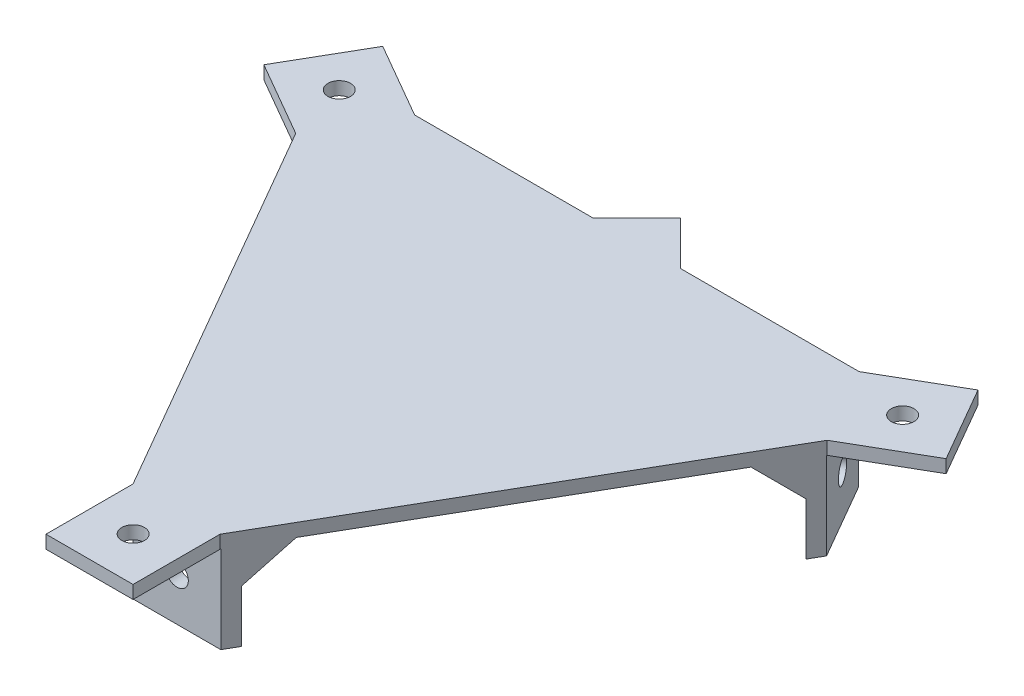
SolidWorks part; units mm, degrees
ref_plane "Ebene vorne" through (0, 0, 0) normal (0, 0, 1) x (1, 0, 0)
ref_plane "Ebene oben" through (0, 0, 0) normal (0, 1, 0) x (1, 0, 0)
ref_plane "Ebene rechts" through (0, 0, 0) normal (1, 0, 0) x (0, 0, -1)
sketch "Skizze1" plane through (0, 0, 0) normal (0, 1, 0) x (1, 0, 0)
  line L0 (0, 0) -> (73.385, 42.3688) construction
  line L1 (73.385, 42.3688) -> (0, -84.7377) construction
  line L2 (0, -84.7377) -> (0, 0) construction
  line L3 (0, 0) -> (-73.385, 42.3688) construction
  line L4 (-73.385, 42.3688) -> (73.385, 42.3688) construction
  line L5 (-73.385, 42.3688) -> (0, -84.7377) construction
  line L6 (10, -5.7735) -> (78.385, 33.7086) construction
  line L7 (0, 11.547) -> (-68.385, 51.0291) construction
  line L8 (10, -84.7377) -> (10, -5.7735) construction
  line L9 (0, 11.547) -> (68.385, 51.0291) construction
  line L10 (-10, -5.7735) -> (-78.385, 33.7086) construction
  line L11 (-10, -84.7377) -> (-10, -5.7735) construction
  line L12 (5, 8.6603) -> (-68.385, 51.0291) construction
  line L13 (-5, 8.6603) -> (68.385, 51.0291) construction
  line L14 (-10, -84.7377) -> (-10, 0) construction
  line L15 (-5, -8.6603) -> (-78.385, 33.7086) construction
  line L16 (5, -8.6603) -> (78.385, 33.7086) construction
  line L17 (10, -84.7377) -> (10, 0) construction
  line L18 (-10, -84.7377) -> (10, -84.7377)
  line L19 (-78.385, 33.7086) -> (-68.385, 51.0291)
  line L20 (68.385, 51.0291) -> (78.385, 33.7086)
  line L21 (-68.385, 51.0291) -> (-51.0645, 41.0291)
  line L22 (-51.0645, 41.0291) -> (51.0645, 41.0291)
  line L23 (51.0645, 41.0291) -> (68.385, 51.0291)
  line L24 (-78.385, 33.7086) -> (-61.0645, 23.7086)
  line L25 (-61.0645, 23.7086) -> (-10, -64.7377)
  line L26 (-10, -64.7377) -> (-10, -84.7377)
  line L27 (10, -84.7377) -> (10, -64.7377)
  line L28 (10, -64.7377) -> (61.0645, 23.7086)
  line L29 (61.0645, 23.7086) -> (78.385, 33.7086)
  line L30 (-51.0645, 41.0291) -> (-61.0645, 23.7086) construction
  line L32 (51.0645, 41.0291) -> (61.0645, 23.7086) construction
  line L33 (-10, -64.7377) -> (10, -64.7377) construction
  line L34 (10, -64.7377) -> (9.736, -64.6288) construction
  point P3 (0, 42.3688)
  point P6 (-36.6925, -21.1844)
  point P9 (36.6925, -21.1844)
  dimension "D1" = 120
  dimension "D2" = 146.77
  dimension "D3" = 10
  dimension "D5" = 20
  dimension "D4" = 10
extrude "Aufsatz-Linear austragen1" add sketch "Skizze1" along normal blind 3
sketch "Skizze3" plane through (0, 0, 0) normal (0, -1, 0) x (1, 0, 0)
  line L0 (0, -51.0291) -> (0, -41.0291) construction
  line L1 (0, -51.0291) -> (-10, -41.0291)
  line L2 (51.0645, -41.0291) -> (-51.0645, -41.0291) construction
  line L3 (-10, -41.0291) -> (10, -41.0291)
  line L4 (10, -41.0291) -> (0, -51.0291)
  line L5 (0, -41.0291) -> (0, 0) construction
  line L6 (-10, -41.0291) -> (-10, 64.7377) construction
  line L7 (-68.385, -51.0291) -> (0, -51.0291) construction
  line L8 (0, -51.0291) -> (-0.0919, -51.1772) construction
extrude "Aufsatz-Linear austragen3" add sketch "Skizze3" against normal up to surface (3 mm away) up to face at (0, 3, 0)
sketch "Skizze2" plane through (0, 0, 0) normal (0, -1, 0) x (1, 0, 0)
  line L0 (-10.0577, 64.6377) -> (10.0577, 64.6377)
  line L1 (-61.0645, -23.7086) -> (-10, 64.7377) construction
  line L2 (10, 64.7377) -> (61.0645, -23.7086) construction
  line L3 (10.0577, 64.6377) -> (11.7898, 61.6377)
  line L4 (11.7898, 61.6377) -> (-11.7898, 61.6377)
  line L5 (-11.7898, 61.6377) -> (-10.0577, 64.6377)
  line L6 (100.0046, 64.7377) -> (-99.9954, 64.7377) construction
  line L7 (61.0068, -23.6086) -> (50.949, -41.0291)
  line L8 (50.949, -41.0291) -> (47.4849, -41.0291)
  line L9 (47.4849, -41.0291) -> (59.2747, -20.6086)
  line L10 (59.2747, -20.6086) -> (61.0068, -23.6086)
  line L11 (-50.949, -41.0291) -> (-61.0068, -23.6086)
  line L12 (-61.0068, -23.6086) -> (-59.2747, -20.6086)
  line L13 (-59.2747, -20.6086) -> (-47.4849, -41.0291)
  line L14 (-47.4849, -41.0291) -> (-50.949, -41.0291)
  point P21 (0, 0)
  dimension "D1" = 3
  dimension "D2" = 0.1
  dimension "D3" = 3
extrude "Aufsatz-Linear austragen2" add sketch "Skizze2" along normal blind 20
sketch "Skizze4" plane through (0, 0, 0) normal (0, -1, 0) x (1, 0, 0)
  line L0 (-11.7898, 61.6377) -> (-16.4086, 53.6377)
  line L1 (-59.2747, -20.6086) -> (-11.7898, 61.6377) construction
  line L2 (-16.4086, 53.6377) -> (-13.4086, 53.6377)
  line L3 (-13.4086, 53.6377) -> (-8.7898, 61.6377)
  line L4 (-11.7898, 61.6377) -> (11.7898, 61.6377) construction
  line L5 (0, 0) -> (0, 61.6377) construction
  line L6 (-11.7898, 61.6377) -> (11.7898, 61.6377) construction
  line L7 (-11.7898, 61.6377) -> (-8.7898, 61.6377)
  line L8 (11.7898, 61.6377) -> (8.7898, 61.6377)
  line L9 (13.4086, 53.6377) -> (8.7898, 61.6377)
  line L10 (16.4086, 53.6377) -> (13.4086, 53.6377)
  line L11 (11.7898, 61.6377) -> (16.4086, 53.6377)
  line L12 (59.2747, -20.6086) -> (54.6559, -12.6086)
  line L13 (54.6559, -12.6086) -> (53.1559, -15.2067)
  line L14 (53.1559, -15.2067) -> (57.7747, -23.2067)
  line L15 (59.2747, -20.6086) -> (57.7747, -23.2067)
  line L16 (47.4849, -41.0291) -> (48.9849, -38.431)
  line L17 (39.7473, -38.431) -> (48.9849, -38.431)
  line L18 (38.2473, -41.0291) -> (39.7473, -38.431)
  line L19 (47.4849, -41.0291) -> (38.2473, -41.0291)
  line L20 (-47.4849, -41.0291) -> (-38.2473, -41.0291)
  line L21 (-38.2473, -41.0291) -> (-39.7473, -38.431)
  line L22 (-39.7473, -38.431) -> (-48.9849, -38.431)
  line L23 (-47.4849, -41.0291) -> (-48.9849, -38.431)
  line L24 (-59.2747, -20.6086) -> (-57.7747, -23.2067)
  line L25 (-53.1559, -15.2067) -> (-57.7747, -23.2067)
  line L26 (-54.6559, -12.6086) -> (-53.1559, -15.2067)
  line L27 (-59.2747, -20.6086) -> (-54.6559, -12.6086)
  point P36 (0, 0)
  dimension "D1" = 3
  dimension "D2" = 8
  dimension "D3" = 3
extrude "Aufsatz-Linear austragen4" add sketch "Skizze4" along normal blind 8
chamfer "Fase1" distance 8 6 edges at (-53.9059, -8, -13.9076) (-38.9973, -8, -39.7301) (38.9973, -8, -39.7301) (53.9059, -8, -13.9076) (14.9086, -8, 53.6377) (-14.9086, -8, 53.6377)
sketch "Skizze5" plane through (0, 3, 0) normal (0, 1, 0) x (1, 0, 0)
  line L0 (-51.0645, 41.0291) -> (-61.0645, 23.7086) construction
  line L1 (51.0645, 41.0291) -> (61.0645, 23.7086) construction
  line L2 (-10.0577, -64.6377) -> (10, -64.7377) construction
  line L3 (-68.385, 51.0291) -> (-61.0645, 23.7086) construction
  line L4 (-78.385, 33.7086) -> (-51.0645, 41.0291) construction
  line L5 (68.385, 51.0291) -> (61.0645, 23.7086) construction
  line L6 (51.0645, 41.0291) -> (78.385, 33.7086) construction
  line L7 (-10.0577, -64.6377) -> (10, -84.7377) construction
  line L8 (-10, -84.7377) -> (10, -64.7377) construction
  circle A0 centre (-64.7247, 37.3688) radius 2.6
  circle A1 centre (64.7247, 37.3688) radius 2.6
  circle A2 centre (-0.0289, -74.6877) radius 2.6
  dimension "D1" = 5.2
extrude "Schnitt-Linear austragen1" cut sketch "Skizze5" against normal up to next
sketch "Skizze6" plane through (53.3798, 0, -30.8188) normal (-0.866, 0, 0.5) x (0.5, 0, 0.866)
  line L0 (0, 0) -> (0, -20) construction
  line L1 (11.7898, -20) -> (-11.7898, -20) construction
  circle A0 centre (0, -10) radius 2.6
  dimension "D1" = 5.2
extrude "Schnitt-Linear austragen2" cut sketch "Skizze6" against normal up to next
sketch "Skizze7" plane through (-53.3798, 0, -30.8188) normal (0.866, 0, 0.5) x (0.5, 0, -0.866)
  line L0 (0, 0) -> (0, -20) construction
  line L1 (11.7898, -20) -> (-11.7898, -20) construction
  circle A0 centre (0, -10) radius 2.6
  dimension "D1" = 5.2
extrude "Schnitt-Linear austragen3" cut sketch "Skizze7" against normal up to next
sketch "Skizze8" plane through (0, 0, 61.6377) normal (0, 0, -1) x (-1, 0, 0)
  line L0 (0, 0) -> (0, -20) construction
  line L1 (11.7898, -20) -> (-11.7898, -20) construction
  circle A0 centre (0, -10) radius 2.6
  dimension "D1" = 5.2
extrude "Schnitt-Linear austragen4" cut sketch "Skizze8" against normal up to next
